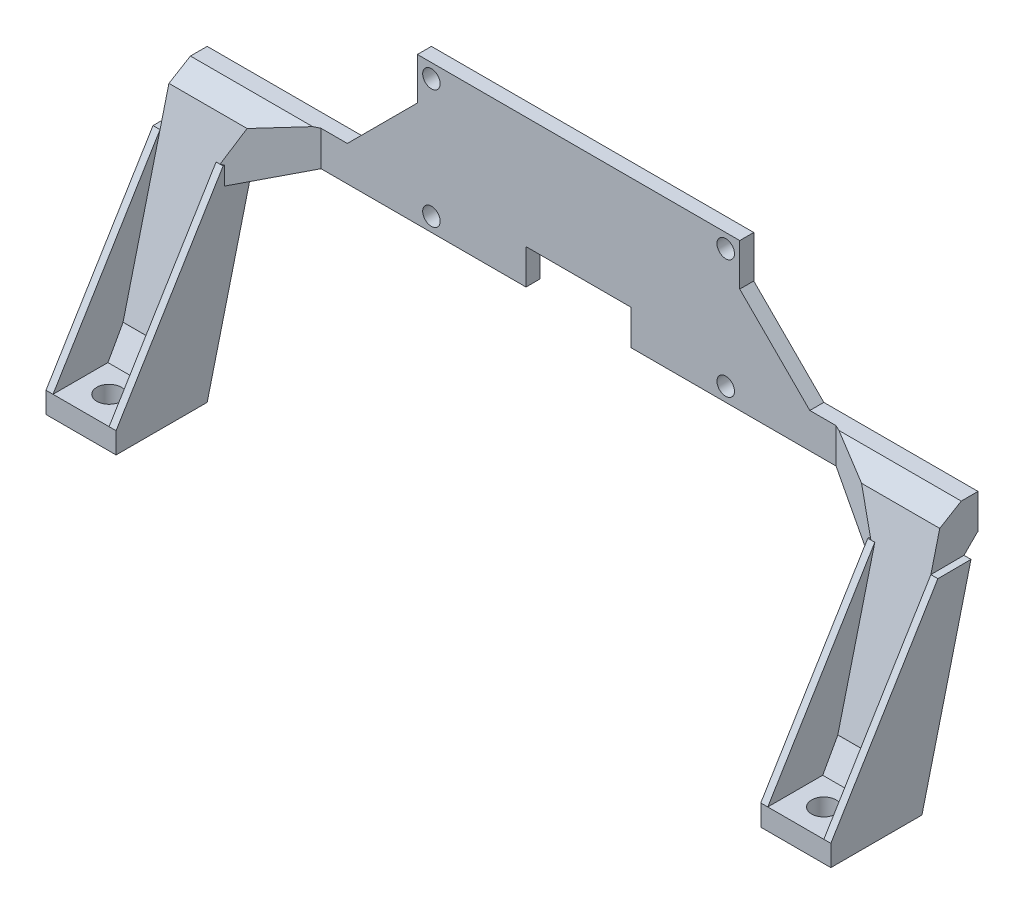
SolidWorks part; units mm, degrees
ref_plane "Front Plane" through (0, 0, 0) normal (0, 0, 1) x (1, 0, 0)
ref_plane "Top Plane" through (0, 0, 0) normal (0, 1, 0) x (1, 0, 0)
ref_plane "Right Plane" through (0, 0, 0) normal (1, 0, 0) x (0, 0, -1)
sketch "Sketch1" plane through (0, 0, 0) normal (0, 0, 1) x (1, 0, 0)
  line L1 (-23, 10.5) -> (23, 10.5)
  line L2 (-23, 10.5) -> (-23, -10.5)
  line L3 (-23, -10.5) -> (23, -10.5)
  line L4 (23, 10.5) -> (23, -10.5)
  line L5 (-23, 10.5) -> (23, -10.5) construction
  line L6 (-23, -10.5) -> (23, 10.5) construction
  line L7 (-7.5, -5.5) -> (7.5, -5.5)
  line L8 (-7.5, -5.5) -> (-7.5, -15.5)
  line L9 (-7.5, -15.5) -> (7.5, -15.5)
  line L10 (7.5, -5.5) -> (7.5, -15.5)
  line L11 (-7.5, -5.5) -> (7.5, -15.5) construction
  line L12 (-7.5, -15.5) -> (7.5, -5.5) construction
  point P0 (0, 0)
  point P6 (0, -10.5)
  dimension "D1" = 46
  dimension "D2" = 21
  dimension "D3" = 10
  dimension "D4" = 15
extrude "Boss-Extrude1" add sketch "Sketch1" along normal blind 2 contours L7 L10 L3 L4 L1 L2 L8
sketch "Sketch2" plane through (0, 0, 2) normal (0, 0, 1) x (1, 0, 0)
  line L0 (-23, 10.5) -> (-23, -10.5) construction
  line L1 (-23, 10.5) -> (23, 10.5) construction
  circle A0 centre (-21, 8.5) radius 1.25
  dimension "D3" = 2.5
  dimension "D1" = 2
  dimension "D2" = 2
extrude "Cut-Extrude1" cut sketch "Sketch2" against normal through all
mirror "Mirror1" about plane through (0, 0, 0) normal (1, 0, 0) of "Cut-Extrude1" second plane through (0, 0, 0) second plane normal (0, 1, 0)
sketch "Sketch4" plane through (0, 0, 0) normal (0, 0, 1) x (1, 0, 0)
  line L1 (-23, -10.5) -> (-55, -10.5)
  line L2 (-23, -10.5) -> (-23, -5.5)
  line L3 (-23, -5.5) -> (-55, -5.5)
  line L4 (-55, -10.5) -> (-55, -5.5)
  dimension "D1" = 55
  dimension "D2" = 5
extrude "Boss-Extrude2" add sketch "Sketch4" along normal blind 2
sketch "Sketch5" plane through (0, 0, 2) normal (0, 0, 1) x (1, 0, 0)
  line L1 (-55, -5.5) -> (-47, -5.5)
  line L2 (-55, -5.5) -> (-55, -40.5)
  line L3 (-55, -40.5) -> (-47, -40.5)
  line L4 (-47, -5.5) -> (-47, -40.5)
  dimension "D1" = 8
  dimension "D2" = 35
extrude "Boss-Extrude3" add sketch "Sketch5" along normal blind 10
chamfer "Chamfer3" distance 7 angle 76 2 edges at (-51, -40.5, 2) (-51, -5.5, 12)
chamfer "Chamfer2" distance 1.9 angle 45 2 edges at (-51, -10.5, 2) (-51, -5.5, 5)
sketch "Sketch6" plane through (0, 0, 12) normal (0, 0, 1) x (1, 0, 0)
  line L1 (-55, -40.5) -> (-47, -40.5)
  line L2 (-55, -40.5) -> (-55, -37.5)
  line L3 (-55, -37.5) -> (-47, -37.5)
  line L4 (-47, -40.5) -> (-47, -37.5)
  dimension "D1" = 3
extrude "Boss-Extrude4" add sketch "Sketch6" along normal blind 10
chamfer "Chamfer4" distance 3.9 angle 29 1 edges at (-51, -37.5, 12)
mirror "Mirror3" about plane through (0, 0, 0) normal (1, 0, 0) of "Chamfer4", "Boss-Extrude4", "Chamfer2", "Chamfer3", "Boss-Extrude3", "Boss-Extrude2"
chamfer "Chamfer1" distance 10 angle 45 2 edges at (-23, -5.5, 1) (23, -5.5, 1)
chamfer "Chamfer5" distance 5 angle 64 12 edges at (-47, -10.5, 1.05) (-47, -11.45, 1.05) (47, -8, 2) (47, -12.4123, 2) (47, -5.5, 2.1957) (47, -6.4218, 3.9256) (47, -10.5, 1.05) (47, -11.45, 1.05) (-47, -8, 2) (-47, -12.4123, 2) (-47, -5.5, 2.1957) (-47, -6.4218, 3.9256)
sketch "Sketch7" plane through (47, 0, 0) normal (-1, 0, 0) x (0, 0, 1)
  line L0 (22, -40.5) -> (9, -40.5)
  line L1 (9, -40.5) -> (2, -12.4245)
  line L2 (2, -12.4245) -> (6.7265, -12.4245)
  line L3 (12, -33.5755) -> (5.4597, -7.3436) construction
  line L4 (6.7265, -12.4245) -> (22, -37.5)
  line L5 (22, -37.5) -> (22, -40.5)
extrude "Boss-Extrude5" add sketch "Sketch7" along normal blind 1
sketch "Sketch8" plane through (55, 0, 0) normal (1, 0, 0) x (0, 0, -1)
  line L0 (-22, -37.5) -> (-22, -40.5)
  line L1 (-22, -40.5) -> (-9, -40.5)
  line L2 (-9, -40.5) -> (-2, -12.4)
  line L3 (-2, -12.4) -> (-6.7265, -12.4245)
  line L4 (-6.7265, -12.4245) -> (-22, -37.5)
extrude "Boss-Extrude6" add sketch "Sketch8" along normal blind 1
mirror "Mirror4" about plane through (0, 0, 0) normal (1, 0, 0) of "Boss-Extrude6", "Boss-Extrude5"
sketch "Sketch9" plane through (0, -37.5, 0) normal (0, 1, 0) x (1, 0, 0)
  line L0 (51, -18) -> (51, -22) construction
  line L1 (47, -22) -> (55, -22) construction
  line L2 (-51, -18) -> (-51, -22) construction
  line L3 (-47, -22) -> (-55, -22) construction
  circle A0 centre (-51, -18) radius 1.75
  circle A1 centre (51, -18) radius 1.75
  dimension "D3" = 3.5
  dimension "D4" = 3.5
  dimension "D1" = 4
  dimension "D2" = 4
extrude "Cut-Extrude2" cut sketch "Sketch9" against normal through all
